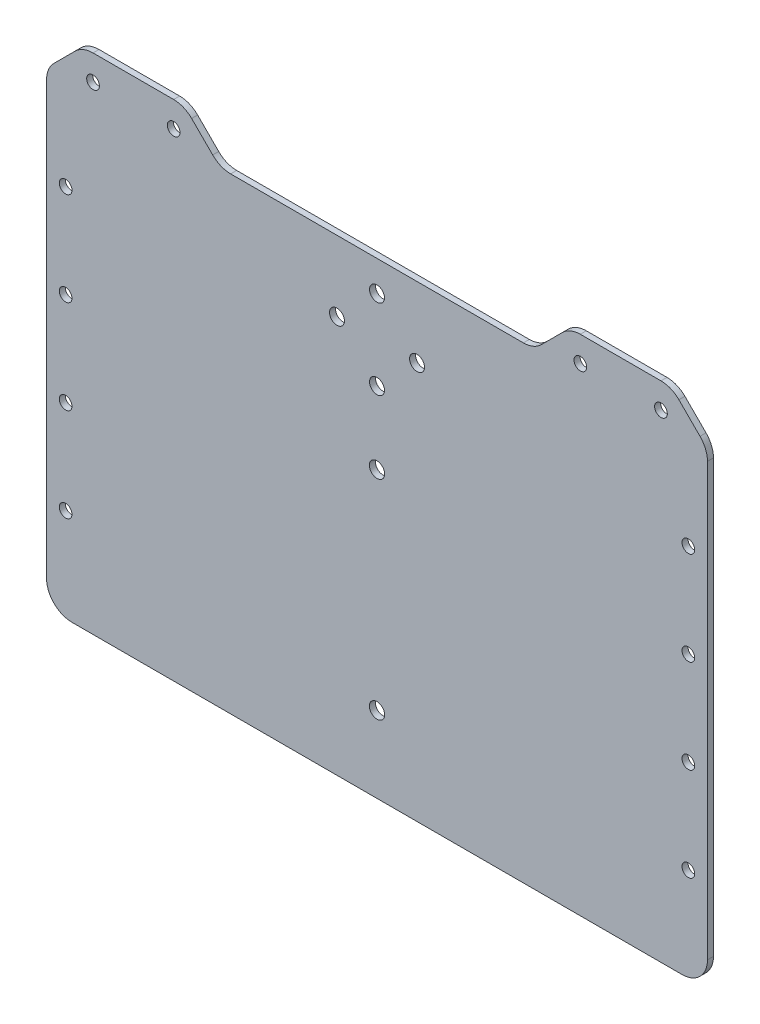
SolidWorks part; units mm, degrees
material "Thornel VCB-20 Carbon Cloth"
ref_plane "Front Plane" through (0, 0, 0) normal (0, 0, 1) x (1, 0, 0)
ref_plane "Top Plane" through (0, 0, 0) normal (0, 1, 0) x (1, 0, 0)
ref_plane "Right Plane" through (0, 0, 0) normal (1, 0, 0) x (0, 0, -1)
sketch "Sketch1" plane through (0, 0, 0) normal (0, 0, 1) x (1, 0, 0)
  line L0 (0, -58.42) -> (0, 58.42) construction
  line L2 (-82.55, 55.7897) -> (-82.55, -52.07)
  line L3 (-76.2, -58.42) -> (76.2, -58.42)
  line L4 (82.55, 55.7897) -> (82.55, -52.07)
  line L5 (-82.55, 58.42) -> (82.55, -58.42) construction
  line L6 (-82.55, -58.42) -> (82.55, 58.42) construction
  line L7 (-80.6901, 60.2799) -> (-75.4296, 65.5404)
  line L8 (-70.9395, 67.4003) -> (-50.8, 67.4003)
  line L9 (-46.3099, 65.5404) -> (-41.0494, 60.2799)
  line L10 (46.3099, 65.5404) -> (41.0494, 60.2799)
  line L11 (70.9395, 67.4003) -> (50.8, 67.4003)
  line L12 (80.6901, 60.2799) -> (75.4296, 65.5404)
  line L13 (-73.5697, 67.4003) -> (-82.55, 67.4003) construction
  line L14 (-82.55, 67.4003) -> (-82.55, 58.42) construction
  line L15 (-36.5592, 58.42) -> (0, 58.42)
  line L16 (0, 58.42) -> (36.5592, 58.42)
  circle A0 centre (-77.7875, -35.052) radius 1.5875
  circle A1 centre (-77.7875, -11.684) radius 1.5875
  circle A2 centre (-77.7875, 11.684) radius 1.5875
  circle A3 centre (-77.7875, 35.052) radius 1.5875
  circle A4 centre (77.7875, 35.052) radius 1.5875
  circle A5 centre (77.7875, 11.684) radius 1.5875
  circle A6 centre (77.7875, -11.684) radius 1.5875
  circle A7 centre (77.7875, -35.052) radius 1.5875
  arc A8 (82.55, 55.7897) -> (80.6901, 60.2799) centre (76.2, 55.7897) ccw
  arc A9 (75.4296, 65.5404) -> (70.9395, 67.4003) centre (70.9395, 61.0503) ccw
  arc A10 (46.3099, 65.5404) -> (50.8, 67.4003) centre (50.8, 61.0503) cw
  arc A11 (41.0494, 60.2799) -> (36.5592, 58.42) centre (36.5592, 64.77) cw
  arc A12 (-36.5592, 58.42) -> (-41.0494, 60.2799) centre (-36.5592, 64.77) cw
  arc A13 (-46.3099, 65.5404) -> (-50.8, 67.4003) centre (-50.8, 61.0503) ccw
  arc A14 (-70.9395, 67.4003) -> (-75.4296, 65.5404) centre (-70.9395, 61.0503) ccw
  arc A15 (-82.55, 55.7897) -> (-80.6901, 60.2799) centre (-76.2, 55.7897) cw
  arc A16 (76.2, -58.42) -> (82.55, -52.07) centre (76.2, -52.07) ccw
  arc A17 (-76.2, -58.42) -> (-82.55, -52.07) centre (-76.2, -52.07) cw
  circle A18 centre (-70.9395, 61.0503) radius 1.5875
  circle A19 centre (-50.8, 61.0503) radius 1.5875
  circle A20 centre (50.8, 61.0503) radius 1.5875
  circle A21 centre (70.9395, 61.0503) radius 1.5875
  point P0 (0, 0)
  point P36 (73.5697, 67.4003)
  point P39 (48.1697, 67.4003)
  point P42 (39.1895, 58.42)
  point P45 (-39.1895, 58.42)
  point P48 (-48.1697, 67.4003)
  dimension "D3" = 3.175
  dimension "D11" = 6.35
  dimension "D12" = 6.35
  dimension "D13" = 3.175
  dimension "D14" = 3.175
  dimension "D1" = 165.1
  dimension "D2" = 116.84
  dimension "D4" = 23.368
  dimension "D5" = 4.7625
  dimension "D7" = 46.736
  dimension "D8" = 12.7
  dimension "D9" = 135
  dimension "D10" = 25.4
  dimension "D6" = 4
extrude "Boss-Extrude1" add sketch "Sketch1" along normal blind 1.5
sketch "Sketch2" plane through (0, 0, 1.5) normal (0, 0, 1) x (1, 0, 0)
  line L0 (0, -39.37) -> (0, 12.7134) construction
  line L1 (0, -58.42) -> (0, 63.5) construction
  line L3 (-82.55, 1.8599) -> (82.55, 1.8599) construction
  line L4 (-82.55, 55.7897) -> (-82.55, -52.07) construction
  line L5 (82.55, -52.07) -> (82.55, 55.7897) construction
  line L7 (-76.2, -58.42) -> (76.2, -58.42) construction
  circle A0 centre (0, -39.37) radius 1.9062
  circle A1 centre (0, 12.7134) radius 1.9062
  dimension "D2" = 3.8125
  dimension "D3" = 3.8125
  dimension "D1" = 52.0834
  dimension "D4" = 19.05
extrude "Cut-Extrude1" cut sketch "Sketch2" against normal through all
sketch "Sketch3" plane through (0, 0, 1.5) normal (0, 0, 1) x (1, 0, 0)
  line L0 (0, 50.8) -> (0, 30.8) construction
  line L1 (-10, 40.8) -> (10, 40.8) construction
  line L2 (-10, 40.8) -> (0, 50.8) construction
  line L3 (0, 50.8) -> (10, 40.8) construction
  line L4 (10, 40.8) -> (0, 30.8) construction
  line L5 (0, 30.8) -> (-10, 40.8) construction
  line L6 (0, 63.5) -> (0, -58.42) construction
  line L8 (-76.2, -58.42) -> (76.2, -58.42) construction
  circle A0 centre (0, 50.8) radius 1.8669
  circle A1 centre (-10, 40.8) radius 1.8669
  circle A2 centre (0, 30.8) radius 1.8669
  circle A3 centre (10, 40.8) radius 1.8669
  dimension "D1" = 3.7338
  dimension "D2" = 12.7
extrude "Cut-Extrude2" cut sketch "Sketch3" against normal through all
equation "\"Top Plate Width\" = 4.5in"
equation "\"Plate Width\" = 4.6in"
equation "\"Plate Thickness\" = 0.375in"
equation "\"Num holes\" = 4"
equation "\"Plate Height\" = 1.25in"
equation "\"D2@Sketch1\"=\"Plate Width\""
equation "\"Plate Clearance Hole Diameter\" = 0.125in"
equation "\"D3@Sketch1\"=\"Plate Clearance Hole Diameter\""
equation "\"Hole Spacing\"= \"Plate Width\" / ( \"Num holes\" + 1 )"
equation "\"D5@Sketch1\"=\"Plate Thickness\" / 2"
equation "\"D7@Sketch1\"= 2 * \"Hole Spacing\""
equation "\"D13@Sketch1\"=\"Plate Clearance Hole Diameter\""
equation "\"D14@Sketch1\"=\"Plate Clearance Hole Diameter\""
equation "\"Plate Tap Hole Diameter\" = 0.116in"
equation "\"Bottom Plate Length\" = 6.5in"
equation "\"D1@Sketch1\"=\"Bottom Plate Length\""
